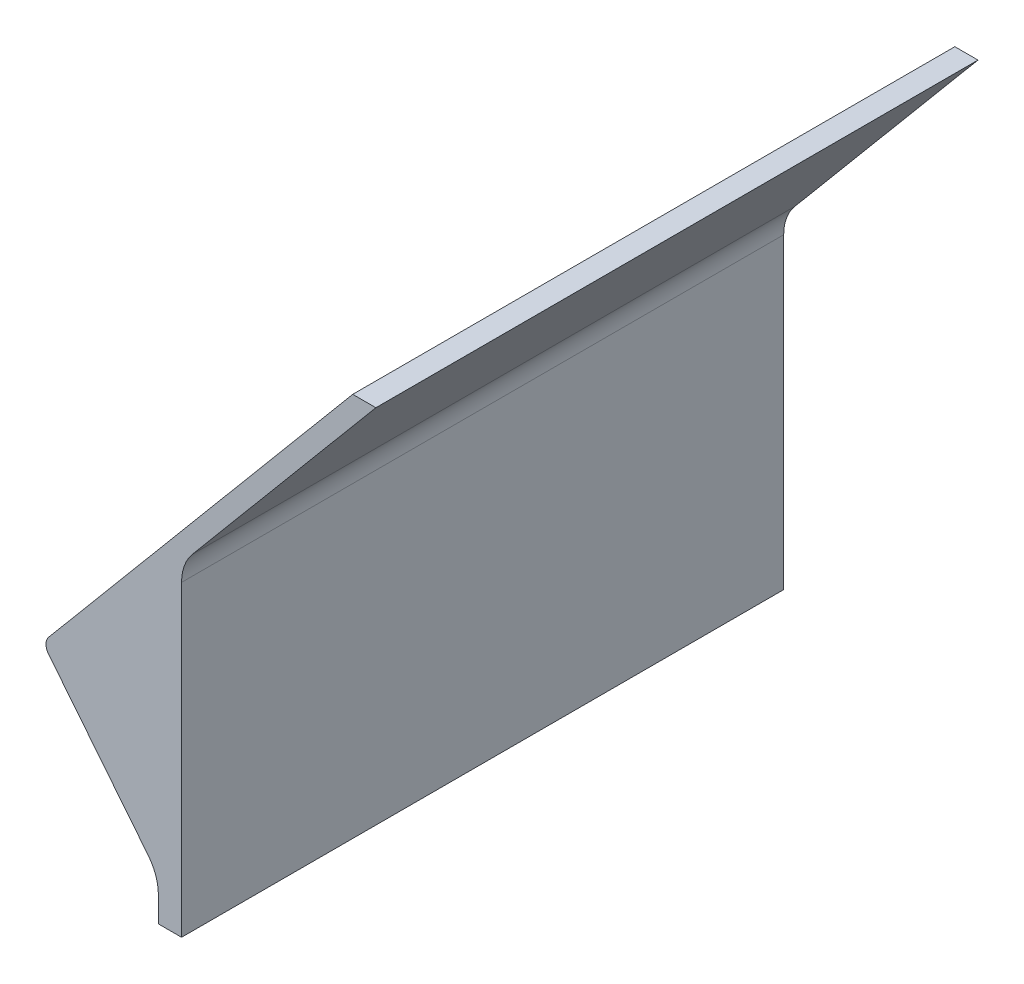
SolidWorks part; units mm, degrees
material "201 Annealed Stainless Steel (SS)"
ref_plane "Front Plane" through (0, 0, 0) normal (0, 0, 1) x (1, 0, 0)
ref_plane "Top Plane" through (0, 0, 0) normal (0, 1, 0) x (1, 0, 0)
ref_plane "Right Plane" through (0, 0, 0) normal (1, 0, 0) x (0, 0, -1)
sketch "Sketch1" plane through (0, 0, 0) normal (0, 0, 1) x (1, 0, 0)
  line L0 (0, 0) -> (0, 70)
  line L1 (0, 70) -> (41.955, 120)
  line L2 (41.955, 120) -> (36.955, 120)
  line L3 (36.955, 120) -> (-30, 40.2062)
  line L4 (-30, 40.2062) -> (-5, 8.9812)
  line L5 (-5, 8.9812) -> (-5, 0)
  line L6 (-5, 0) -> (0, 0)
  line L7 (-5, 0) -> (-45, 0) construction
  line L8 (-30, 0) -> (-30, 78.9136) construction
  dimension "D1" = 5
  dimension "D2" = 5
  dimension "D3" = 140
  dimension "D4" = 120
  dimension "D5" = 70
  dimension "D6" = 40
  dimension "D7" = 25
  dimension "D8" = 40
extrude "Funnel - Right Side" add sketch "Sketch1" along normal blind 130
fillet "Fillet2" radius 10 2 edges at (0, 70, 65) (-5, 8.9812, 65)
fillet "Fillet3" radius 2.5 1 edges at (-30, 40.2062, 65)
